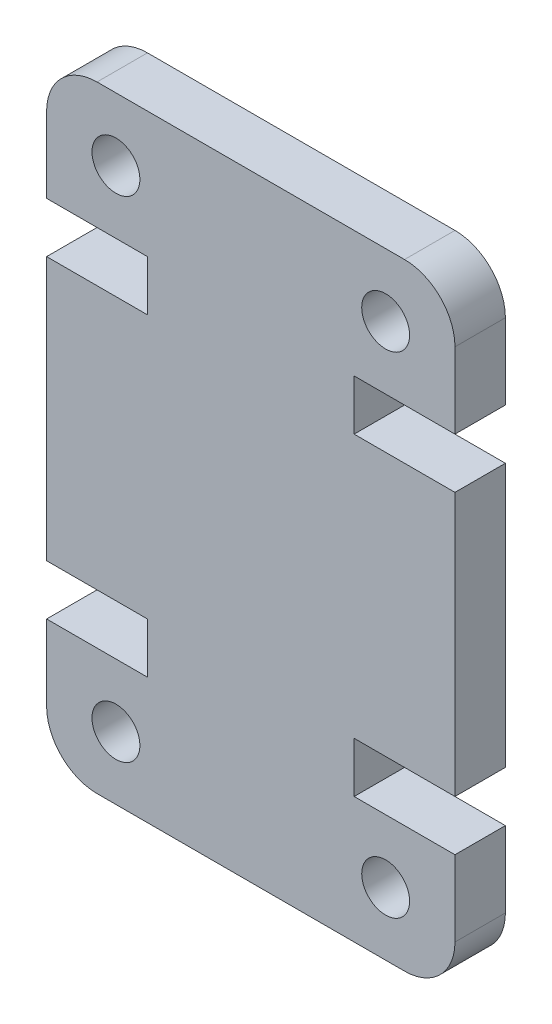
SolidWorks part; units mm, degrees
ref_plane "Front Plane" through (0, 0, 0) normal (0, 0, 1) x (1, 0, 0)
ref_plane "Top Plane" through (0, 0, 0) normal (0, 1, 0) x (1, 0, 0)
ref_plane "Right Plane" through (0, 0, 0) normal (1, 0, 0) x (0, 0, -1)
sketch "Sketch1" plane through (0, 0, 0) normal (0, 0, 1) x (1, 0, 0)
  line L0 (0, 17.45) -> (0, 7)
  line L1 (16.2, 5) -> (16.2, 2)
  line L2 (12.2, 5) -> (16.2, 5)
  line L3 (2, 0) -> (14.2, 0)
  line L4 (16.2, 7) -> (12.2, 7)
  line L5 (12.2, 7) -> (12.2, 5)
  line L6 (16.2, 17.45) -> (16.2, 7)
  line L7 (0, 19.45) -> (0, 22.45)
  line L8 (4, 19.45) -> (0, 19.45)
  line L9 (0, 17.45) -> (4, 17.45)
  line L10 (4, 7) -> (4, 5)
  line L11 (4, 17.45) -> (4, 19.45)
  line L12 (0, 7) -> (4, 7)
  line L13 (4, 5) -> (0, 5)
  line L14 (12.2, 17.45) -> (12.2, 19.45)
  line L15 (16.2, 17.45) -> (12.2, 17.45)
  line L16 (2, 24.45) -> (14.2, 24.45)
  line L17 (12.2, 19.45) -> (16.2, 19.45)
  line L18 (16.2, 19.45) -> (16.2, 22.45)
  line L19 (0, 5) -> (0, 2)
  line L20 (0, 12.225) -> (16.2, 12.225) construction
  line L21 (8.1, 24.45) -> (8.1, 0) construction
  circle A0 centre (13.45, 2.5) radius 0.95
  arc A1 (16.2, 2) -> (14.2, 0) centre (14.2, 2) cw
  circle A2 centre (2.75, 21.95) radius 0.95
  arc A3 (0, 2) -> (2, 0) centre (2, 2) ccw
  arc A4 (0, 22.45) -> (2, 24.45) centre (2, 22.45) cw
  circle A5 centre (2.75, 2.5) radius 0.95
  arc A6 (16.2, 22.45) -> (14.2, 24.45) centre (14.2, 22.45) ccw
  circle A7 centre (13.45, 21.95) radius 0.95
  point P17 (8.1, 12.225)
  dimension "D1" = 1.9
  dimension "D2" = 2
  dimension "D3" = 2.75
  dimension "D4" = 8.1
  dimension "D5" = 2.5
  dimension "D8" = 12.225
  dimension "D6" = 5
extrude "Boss-Extrude1" add sketch "Sketch1" along normal blind 4
sketch "Sketch2" plane through (0, 0, 0) normal (0, 0, -1) x (-1, 0, 0)
  line L0 (0, 0) -> (0, 24.45)
  line L1 (0, 24.45) -> (-16.2, 24.45)
  line L2 (-16.2, 24.45) -> (-16.2, 0)
  line L3 (-16.2, 0) -> (0, 0)
extrude "Cut-Extrude1" cut sketch "Sketch2" against normal blind 2
equation "\"D4@Sketch1\"= \"fingerWidth@parametersSketch@prostheticParameters.SLDPRT\" / 2 'MIP Width"
equation "\"D8@Sketch1\"= ( ( \"HL@parametersSketch@prostheticParameters.SLDPRT\" * 0.17 ) - 4 - 3 ) / 2 'MIP Length - Sil. Sht MIP - Sil. Sht DIP"
equation "\"D1@Sketch1\"= 1.5 + \"tol1@parametersSketch@prostheticParameters.SLDPRT\""
